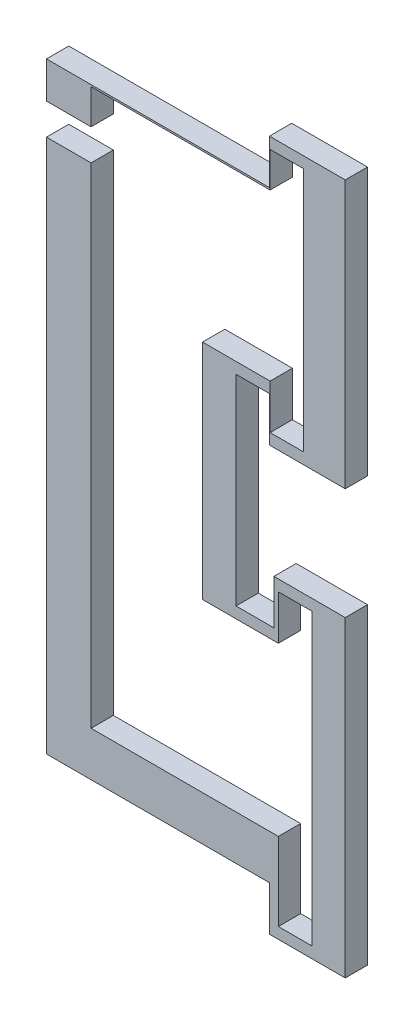
SolidWorks part; units mm, degrees
ref_plane "Front Plane" through (0, 0, 0) normal (0, 0, 1) x (1, 0, 0)
ref_plane "Top Plane" through (0, 0, 0) normal (0, 1, 0) x (1, 0, 0)
ref_plane "Right Plane" through (0, 0, 0) normal (1, 0, 0) x (0, 0, -1)
sketch "Sketch1" plane through (0, 0, 0) normal (0, 0, 1) x (1, 0, 0)
  line L0 (0, 0) -> (0, 119.8)
  line L4 (10, 10) -> (10, 119.8)
  line L5 (10, 119.8) -> (0, 119.8)
  line L6 (0, 126.8) -> (0, 135)
  line L7 (0, 135) -> (50, 135)
  line L8 (50.15, 135) -> (50.15, 134.6)
  line L9 (50.15, 134.6) -> (10, 134.6)
  line L10 (10, 134.6) -> (10, 126.8)
  line L11 (10, 126.8) -> (0, 126.8)
  line L12 (10, 10) -> (52, 10)
  line L20 (59.5, -7.5) -> (59.5, 57.5)
  line L24 (67, 60) -> (67, -10)
  line L32 (35, 47.5) -> (35, 97.5)
  line L33 (35, 97.5) -> (50.15, 97.5)
  line L36 (42.5, 95) -> (42.5, 50)
  line L41 (57.65, 142.5) -> (50.15, 142.5)
  line L44 (67, 145) -> (67, 85)
  line L47 (50.15, 135) -> (50.15, 142.5)
  line L48 (50, 135) -> (50, 145)
  line L49 (50, 145) -> (67, 145)
  line L55 (50.15, 97.5) -> (50.15, 95)
  line L78 (50.15, 87.5) -> (57.65, 87.5)
  line L82 (42.5, 95) -> (50, 95)
  line L83 (50.15, 95) -> (50.15, 87.5)
  line L84 (67, 85) -> (50, 85)
  line L85 (50, 85) -> (50, 95)
  line L86 (35, 47.5) -> (52, 47.5)
  line L87 (52, 47.5) -> (52, 52.5)
  line L88 (51, 50) -> (42.5, 50)
  line L89 (67, 60) -> (51, 60)
  line L90 (51, 60) -> (51, 59.8508)
  line L91 (52, 57.5) -> (59.5, 57.5)
  line L92 (52, 52.5) -> (52, 57.5)
  line L95 (51, 59.8508) -> (51, 50)
  line L97 (67, -10) -> (50, -10)
  line L98 (50, -10) -> (50, -7.5)
  line L100 (50, -7.5) -> (50, 0)
  line L101 (59.5, -7.5) -> (52, -7.5)
  line L105 (0, 0) -> (50, 0)
  line L106 (52, 10) -> (52, -3.1688)
  line L107 (52, -3.1688) -> (52, -7.5)
  line L108 (57.65, 142.5) -> (57.65, 87.5)
  dimension "D3" = 7.5
  dimension "D4" = 0.15
  dimension "D5" = 7.5
  dimension "D6" = 7.5
  dimension "D7" = 0.15
  dimension "D8" = 1
  dimension "D12" = 0.4
  dimension "D13" = 50
  dimension "D15" = 0.4
  dimension "D10" = 109.8
  dimension "D11" = 70
  dimension "D16" = 7.5
  dimension "D14" = 7.5
  dimension "D17" = 7.5
  dimension "D19" = 2.5
  dimension "D21" = 10
  dimension "D23" = 2
  dimension "D24" = 50
  dimension "D25" = 8.2
  dimension "D22" = 10
  dimension "D18" = 2.5
  dimension "D26" = 60
  dimension "D27" = 7.5
  dimension "D28" = 7.5
  dimension "D29" = 2.5
  dimension "D30" = 2.5
  dimension "D31" = 50
  dimension "D9" = 2.5
  dimension "D32" = 2.5
  dimension "D33" = 7.5
  dimension "D34" = 7.5
  dimension "D20" = 7.5
extrude "Boss-Extrude1" add sketch "Sketch1" along normal blind 5
equation "\"A.L\"= 0.07m"
equation "\"A.h\"= 0.0075m"
equation "\"A.d\"= 0.003m"
equation "\"A.delta\"= 45.0001"
equation "\"A.w\"= 0.02m"
equation "\"A.v\"= 0.03m"
equation "\"B.L\"= 0.06m"
equation "\"B.h\"= 0.0075m"
equation "\"C.h\"= 0.0004m"
equation "\"C.d\"= 0.003m"
equation "\"C.L\"= 0.04m"
equation "\"C.wmax\"= 0.008m"
equation "\"a_h\"= 0.001m"
equation "\"a_d\"= 0.003m"
equation "\"a_L\"= 0.0075m"
equation "\"b_h\"= 0.00015m"
equation "\"b_d\"= 0.003m"
equation "\"b_L\"= 0.0075m"
equation "\"c_h\"= 0.00015m"
equation "\"c_d\"= 0.003m"
equation "\"c_L\"= 0.0075m"
equation "\"S.h\"= 0.01m"
equation "\"S.L\"= 0.1178m"
equation "\"D4@Sketch1\"=\"c_h\""
equation "\"D5@Sketch1\"=\"c_L\""
equation "\"d_h\"= 0.002m"
equation "\"d_L\"= 0.0075m"
equation "\"d_d\"= 0.003m"
equation "\"D6@Sketch1\"=\"b_L\""
equation "\"D7@Sketch1\"=\"b_h\""
equation "\"D8@Sketch1\"=\"a_h\""
equation "\"D12@Sketch1\"=\"C.h\""
equation "\"D13@Sketch1\"=\"C.L\"+\"S.h\""
equation "\"D15@Sketch1\"=\"C.h\""
equation "\"A.t\"= 0.0025m"
equation "\"A.s\"= 0.0075m"
equation "\"D11@Sketch1\"=\"A.L\""
equation "\"D16@Sketch1\"=\"A.s\""
equation "\"D17@Sketch1\"=\"A.s\""
equation "\"D19@Sketch1\"=\"A.t\""
equation "\"D21@Sketch1\"=\"S.h\""
equation "\"D23@Sketch1\"=\"d_h\""
equation "\"D24@Sketch1\"=\"C.L\"+\"S.h\""
equation "\"D25@Sketch1\"=\"C.h\"/2+\"C.wmax\""
equation "\"D22@Sketch1\"=\"S.h\""
equation "\"D18@Sketch1\"=\"A.t\""
equation "\"B.t\"= 0.0025m"
equation "\"B.s\"= 0.0075m"
equation "\"D26@Sketch1\"=\"B.L\""
equation "\"D27@Sketch1\"=\"B.s\""
equation "\"D28@Sketch1\"=\"B.s\""
equation "\"D29@Sketch1\"=\"B.t\""
equation "\"D30@Sketch1\"=\"B.t\""
equation "\"D14@Sketch1\"=\"A.h\""
equation "\"D.L\"= 0.05m"
equation "\"D.h\"= 0.0075m"
equation "\"D.s\"= 0.0075m"
equation "\"D.t\"= 0.0025m"
equation "\"D31@Sketch1\"=\"D.L\""
equation "\"D3@Sketch1\"=\"D.h\""
equation "\"D9@Sketch1\"=\"D.t\""
equation "\"D33@Sketch1\"=\"a_L\""
equation "\"D34@Sketch1\"=\"D.s\""
equation "\"D32@Sketch1\"=\"D.t\""
equation "\"D20@Sketch1\"=\"d_L\""
equation "\"D10@Sketch1\"=\"S.L\"-\"C.wmax\""
